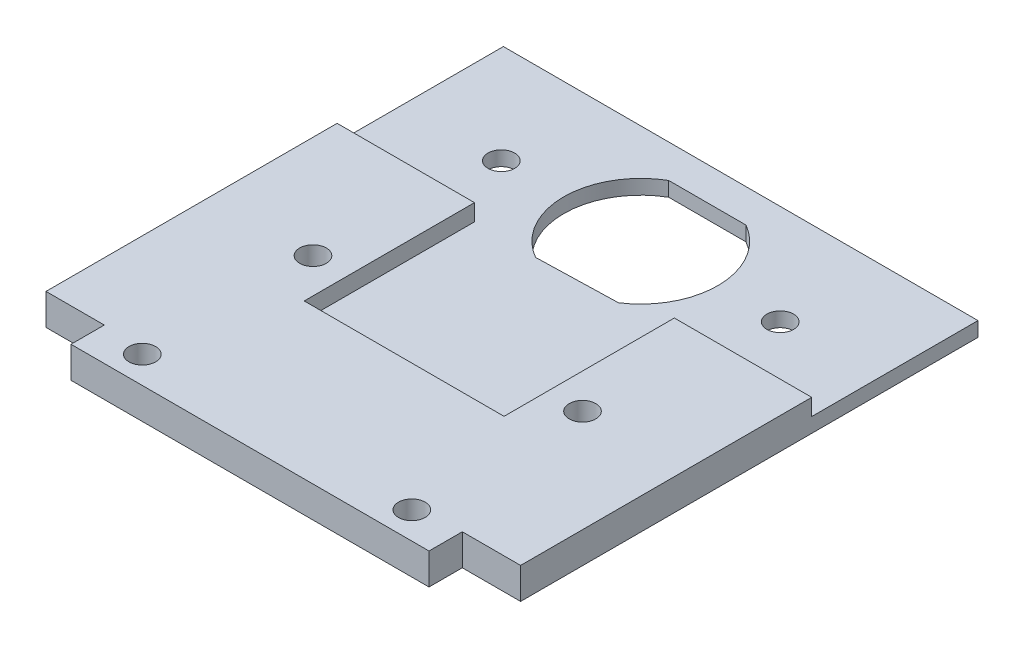
SolidWorks part; units mm, degrees
ref_plane "Ebene vorne" through (0, 0, 0) normal (0, 0, 1) x (1, 0, 0)
ref_plane "Ebene oben" through (0, 0, 0) normal (0, 1, 0) x (1, 0, 0)
ref_plane "Ebene rechts" through (0, 0, 0) normal (1, 0, 0) x (0, 0, -1)
sketch "Skizze1" plane through (0, 0, 0) normal (0, 1, 0) x (1, 0, 0)
  line L0 (0, 4) -> (7, 4)
  line L1 (7, 0) -> (17.7787, 0)
  line L2 (0, 4) -> (0, 58.9339)
  line L3 (0, 58.9339) -> (57, 58.9339)
  line L4 (57, 4) -> (57, 58.9339)
  line L5 (7, 4) -> (7, 0)
  line L9 (50, 0) -> (50, 4)
  line L10 (50, 4) -> (57, 4)
  line L11 (38.7787, 0) -> (50, 0)
  line L12 (17.7787, 0) -> (38.7787, 0)
  dimension "D1" = 57
  dimension "D3" = 7
  dimension "D4" = 4
  dimension "D7" = 4
  dimension "D8" = 7
extrude "Aufsatz-Linear austragen1" add sketch "Skizze1" against normal blind 3.75
sketch "Skizze16" plane through (0, 0, 0) normal (0, 1, 0) x (1, 0, 0)
  line L0 (57, 58.9339) -> (57, 38.9637)
  line L1 (57, 4) -> (57, 58.9339) construction
  line L2 (57, 38.9637) -> (0, 38.9637)
  line L3 (0, 58.9339) -> (0, 4) construction
  line L4 (0, 38.9637) -> (0, 58.9339)
  line L5 (0, 58.9339) -> (57, 58.9339)
extrude "Schnitt-Linear austragen6" cut sketch "Skizze16" against normal blind 2
sketch "Skizze3" plane through (0, -2, 0) normal (0, 1, 0) x (1, 0, 0)
  line L0 (57, 58.9339) -> (0, 58.9339) construction
  line L1 (33.5654, 39.1941) -> (23.8565, 38.9339)
  line L2 (57, 4) -> (57, 38.9637) construction
  line L3 (38.5, 38.9339) -> (18.5, 38.9339) construction
  line L4 (33.1435, 54.9339) -> (23.8565, 54.9339)
  line L5 (18.5, 54.9339) -> (38.5, 54.9339) construction
  arc A0 (33.5654, 39.1941) -> (33.1435, 54.9339) centre (28.5, 46.9339) ccw
  arc A1 (23.8565, 54.9339) -> (23.8565, 38.9339) centre (28.5, 46.9339) ccw
  dimension "D3" = 18.5
  dimension "D1" = 12
  dimension "D2" = 28.5
extrude "Schnitt-Linear austragen1" cut sketch "Skizze3" against normal blind 2
ref_plane "Ebene1" through (28.5, 0, 0) normal (-1, 0, 0) x (0, 0, 1)
sketch "Skizze10" plane through (0, -2, 0) normal (0, 1, 0) x (1, 0, 0)
  line L1 (57, 58.9339) -> (0, 58.9339) construction
  line L2 (57, 4) -> (57, 38.9637) construction
  line L3 (0, 38.9637) -> (0, 4) construction
  circle A0 centre (45.25, 46.9339) radius 1.6
  circle A1 centre (11.75, 46.9339) radius 1.6
  dimension "D5" = 3.2
  dimension "D1" = 12
  dimension "D2" = 12
  dimension "D3" = 11.75
  dimension "D4" = 11.75
extrude "Schnitt-Linear austragen3" cut sketch "Skizze10" against normal blind 3.2
ref_plane "Ebene2" through (0, 0, -20.9339) normal (0, 0, -1) x (-1, 0, 0)
sketch "Skizze17" plane through (0, 0, 0) normal (0, 1, 0) x (1, 0, 0)
  line L0 (7, 0) -> (50, 0) construction
  line L1 (7, 0) -> (50, 0) construction
  line L2 (57, 4) -> (57, 38.9637) construction
  line L3 (0, 38.9637) -> (0, 4) construction
  circle A0 centre (44.6847, 3.25) radius 1.6
  circle A1 centre (44.6847, 23.75) radius 1.6
  circle A2 centre (12.3153, 3.25) radius 1.6
  circle A3 centre (12.3153, 23.75) radius 1.6
  point P16 (0, 0)
  point P17 (0, 0)
  point P18 (0, 0)
  point P19 (0, 0)
  point P20 (0, 0)
  point P21 (0, 0)
  dimension "D1" = 3.2
  dimension "D2" = 3.2
  dimension "D3" = 3.2
  dimension "D4" = 3.25
  dimension "D5" = 20.5
  dimension "D6" = 20.5
  dimension "D7" = 3.25
  dimension "D8" = 12.3153
  dimension "D9" = 12.3153
extrude "Schnitt-Linear austragen7" cut sketch "Skizze17" against normal blind 4
sketch "Skizze18" plane through (0, 0, 0) normal (0, 1, 0) x (1, 0, 0)
  line L0 (0, 38.9637) -> (57, 38.9637) construction
  line L1 (40.5, 38.9637) -> (16.5, 38.9637)
  line L2 (40.5, 38.9637) -> (40.5, 18.5122)
  line L3 (40.5, 18.5122) -> (16.5, 18.5122)
  line L4 (16.5, 38.9637) -> (16.5, 18.5122)
  line L5 (40, 19.0386) -> (40, 38.5386) construction
  dimension "D1" = 20.4515
  dimension "D2" = 24
  dimension "D3" = 0.5
extrude "Schnitt-Linear austragen8" cut sketch "Skizze18" against normal blind 2
ref_plane "Ebene3" through (33.1435, -2, -54.9339) normal (0, 1, 0) x (1, 0, 0)
